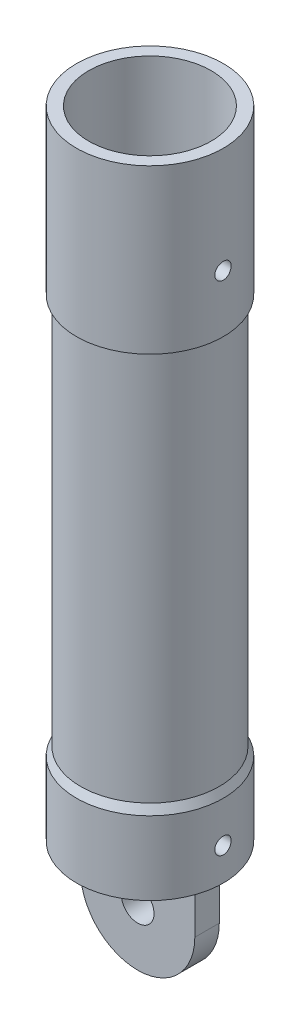
SolidWorks part; units mm, degrees
ref_plane "Front Plane" through (0, 0, 0) normal (0, 0, 1) x (1, 0, 0)
ref_plane "Top Plane" through (0, 0, 0) normal (0, 1, 0) x (1, 0, 0)
ref_plane "Right Plane" through (0, 0, 0) normal (1, 0, 0) x (0, 0, -1)
sketch "Sketch1" plane through (0, 0, 0) normal (0, 0, 1) x (1, 0, 0)
  line L0 (0, 78) -> (0, 0) construction
  line L1 (0, 0) -> (-9, 0)
  line L2 (-9, 0) -> (-9, 9)
  line L3 (-9, 9) -> (-8.5, 10)
  line L4 (-8.5, 10) -> (-8.5, 58)
  line L5 (-8.5, 58) -> (-9, 58)
  line L6 (-9, 58) -> (-9, 78)
  line L7 (-9, 78) -> (-7.5, 78)
  line L8 (-7.5, 78) -> (-7.5, 2)
  line L9 (-7.5, 2) -> (0, 2)
  line L10 (0, 2) -> (0, 0)
  dimension "D1" = 18
  dimension "D2" = 17
  dimension "D3" = 1
  dimension "D4" = 18
  dimension "D5" = 1
  dimension "D6" = 2
  dimension "D7" = 9
  dimension "D8" = 20
  dimension "D9" = 48
revolve "Revolve1" add sketch "Sketch1" angle 360 about L0
sketch "Sketch2" plane through (0, 0, 0) normal (0, 0, 1) x (1, 0, 0)
  line L0 (-7, 0) -> (7, 0)
  line L1 (-9, 0) -> (9, 0) construction
  line L2 (7, 0) -> (7, -6)
  line L3 (-7, 0) -> (-7, -6)
  line L4 (7, -6) -> (-7, -6) construction
  arc A0 (-7, -6) -> (7, -6) centre (0, -6) ccw
  circle A1 centre (0, -6) radius 2
  point P7 (0, 0)
  dimension "D1" = 6
  dimension "D3" = 4
  dimension "D2" = 14
extrude "Boss-Extrude1" add sketch "Sketch2" along normal blind 1.5 and the other way blind 1.5
sketch "Sketch3" plane through (0, 0, 0) normal (1, 0, 0) x (0, 0, -1)
  line L0 (0, 78) -> (0, 0) construction
  line L1 (7.5, 78) -> (-7.5, 78) construction
  line L2 (-9, 0) -> (9, 0) construction
  line L3 (9, 78) -> (-9, 78) construction
  circle A0 centre (0, 65) radius 1
  circle A1 centre (0, 4) radius 1
  dimension "D1" = 2
  dimension "D2" = 2
  dimension "D3" = 4
  dimension "D4" = 13
extrude "Cut-Extrude1" cut sketch "Sketch3" along normal blind 50
